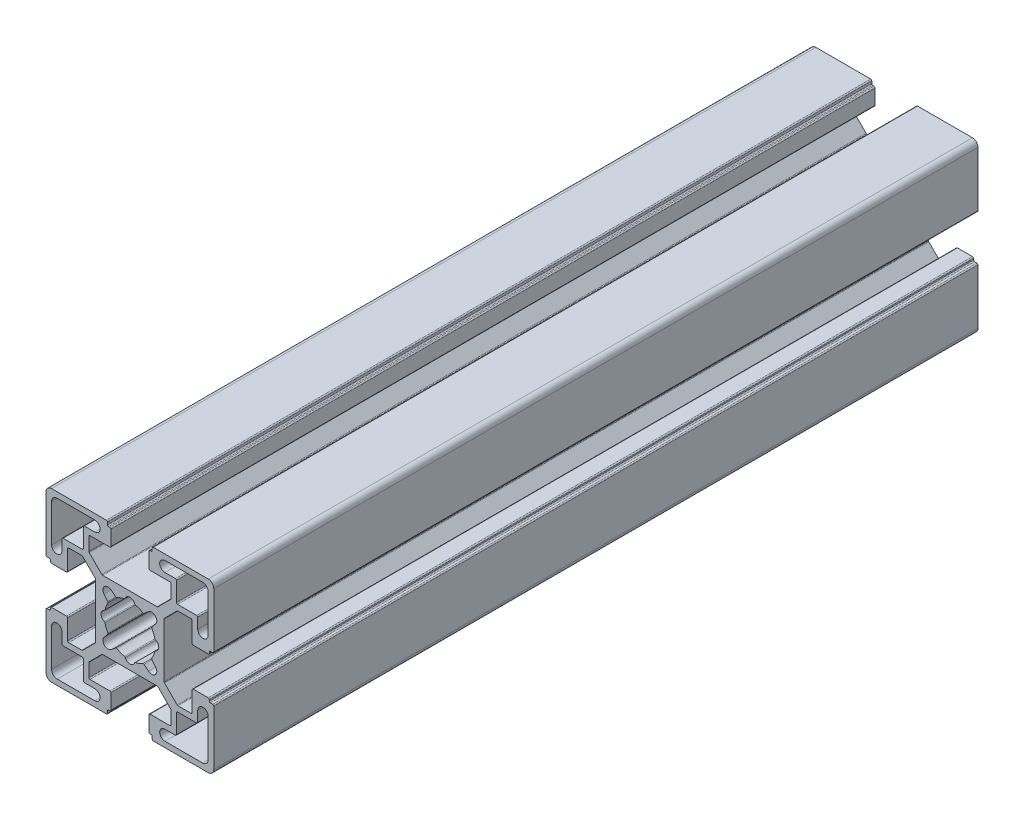
SolidWorks part; units mm, degrees
material "6063-T5"
ref_plane "Plane1" through (0, 0, 0) normal (0, 0, 1) x (1, 0, 0)
ref_plane "Plane2" through (0, 0, 0) normal (0, 1, 0) x (1, 0, 0)
ref_plane "Plane3" through (0, 0, 0) normal (1, 0, 0) x (0, 0, -1)
sketch "Sketch1" plane through (0, 0, 0) normal (0, 0, 1) x (1, 0, 0)
  line L0 (-3.8182, 5.9298) -> (-5.0112, 6.9114)
  line L1 (-6.9114, 5.0112) -> (-5.9298, 3.8182)
  line L2 (-5.9298, -3.8182) -> (-6.9114, -5.0112)
  line L3 (-5.0112, -6.9114) -> (-3.8182, -5.9298)
  line L4 (3.8182, -5.9298) -> (5.0112, -6.9114)
  line L5 (6.9114, -5.0112) -> (5.9298, -3.8182)
  line L6 (5.9298, 3.8182) -> (6.9114, 5.0112)
  line L7 (5.0112, 6.9114) -> (3.8182, 5.9298)
  line L8 (-19.5, -21) -> (-9.4, -21)
  line L9 (-9.4, -18.2) -> (-12.2, -18.2)
  line L10 (-12.5, -17.9) -> (-12.5, -12.8)
  line L11 (-12.8, -12.5) -> (-17.9, -12.5)
  line L12 (-18.2, -12.2) -> (-18.2, -9.4)
  line L13 (-21, -9.4) -> (-21, -19.5)
  line L14 (17.9, -12.5) -> (12.8, -12.5)
  line L15 (12.5, -12.8) -> (12.5, -17.9)
  line L16 (12.2, -18.2) -> (9.4, -18.2)
  line L17 (9.4, -21) -> (19.5, -21)
  line L18 (21, -19.5) -> (21, -9.4)
  line L19 (18.2, -9.4) -> (18.2, -12.2)
  line L20 (19.5, 21) -> (9.4, 21)
  line L21 (9.4, 18.2) -> (12.2, 18.2)
  line L22 (12.5, 17.9) -> (12.5, 12.8)
  line L23 (12.8, 12.5) -> (17.9, 12.5)
  line L24 (18.2, 12.2) -> (18.2, 9.4)
  line L25 (21, 9.4) -> (21, 19.5)
  line L26 (-18.2, 9.4) -> (-18.2, 12.2)
  line L27 (-17.9, 12.5) -> (-12.8, 12.5)
  line L28 (-12.5, 12.8) -> (-12.5, 17.9)
  line L29 (-12.2, 18.2) -> (-9.4, 18.2)
  line L30 (-9.4, 21) -> (-19.5, 21)
  line L31 (-21, 19.5) -> (-21, 9.4)
  line L32 (22.5, 6.3) -> (22.5, 21)
  line L33 (21.6, 6) -> (22.2, 6)
  line L34 (21.3, 5.4) -> (21.3, 5.7)
  line L36 (16.7, 10.7) -> (16.7, 5.4)
  line L37 (12.892, 11) -> (16.4, 11)
  line L38 (9.2879, 7.5201) -> (12.6799, 10.9121)
  line L39 (9.2, -7.308) -> (9.2, 7.308)
  line L40 (12.6799, -10.9121) -> (9.2879, -7.5201)
  line L41 (16.4, -11) -> (12.892, -11)
  line L42 (16.7, -5.4) -> (16.7, -10.7)
  line L44 (21.3, -5.7) -> (21.3, -5.4)
  line L45 (22.2, -6) -> (21.6, -6)
  line L46 (22.5, -21) -> (22.5, -6.3)
  line L47 (6.3, -22.5) -> (21, -22.5)
  line L48 (6, -21.6) -> (6, -22.2)
  line L49 (5.4, -21.3) -> (5.7, -21.3)
  line L51 (10.7, -16.7) -> (5.4, -16.7)
  line L52 (11, -12.892) -> (11, -16.4)
  line L53 (7.5201, -9.2879) -> (10.9121, -12.6799)
  line L54 (-7.4322, -9.2) -> (7.308, -9.2)
  line L55 (-10.9121, -12.6799) -> (-7.4322, -9.2)
  line L56 (-11, -16.4) -> (-11, -12.892)
  line L57 (-5.4, -16.7) -> (-10.7, -16.7)
  line L59 (-5.7, -21.3) -> (-5.4, -21.3)
  line L60 (-6, -22.2) -> (-6, -21.6)
  line L61 (-21, -22.5) -> (-6.3, -22.5)
  line L62 (-22.5, -6.3) -> (-22.5, -21)
  line L63 (-21.6, -6) -> (-22.2, -6)
  line L64 (-21.3, -5.4) -> (-21.3, -5.7)
  line L66 (-16.7, -10.7) -> (-16.7, -5.4)
  line L67 (-12.892, -11) -> (-16.4, -11)
  line L68 (-9.2879, -7.5201) -> (-12.6799, -10.9121)
  line L69 (-9.2, 7.308) -> (-9.2, -7.308)
  line L70 (-12.6799, 10.9121) -> (-9.2879, 7.5201)
  line L71 (-16.4, 11) -> (-12.892, 11)
  line L72 (-16.7, 5.4) -> (-16.7, 10.7)
  line L74 (-21.3, 5.7) -> (-21.3, 5.4)
  line L75 (-22.2, 6) -> (-21.6, 6)
  line L76 (-22.5, 21) -> (-22.5, 6.3)
  line L77 (-6.3, 22.5) -> (-21, 22.5)
  line L78 (-6, 21.6) -> (-6, 22.2)
  line L79 (-5.4, 21.3) -> (-5.7, 21.3)
  line L81 (-10.7, 16.7) -> (-5.4, 16.7)
  line L82 (-11, 12.892) -> (-11, 16.4)
  line L83 (-7.5201, 9.2879) -> (-10.9121, 12.6799)
  line L84 (7.308, 9.2) -> (-7.308, 9.2)
  line L85 (10.9121, 12.6799) -> (7.5201, 9.2879)
  line L86 (11, 16.4) -> (11, 12.892)
  line L87 (5.4, 16.7) -> (10.7, 16.7)
  line L89 (5.7, 21.3) -> (5.4, 21.3)
  line L90 (6, 22.2) -> (6, 21.6)
  line L91 (21, 22.5) -> (6.3, 22.5)
  line L92 (-5.1, 17) -> (-5.1, 21)
  line L93 (-21, 5.1) -> (-17, 5.1)
  line L94 (-17, -5.1) -> (-21, -5.1)
  line L95 (-5.1, -21) -> (-5.1, -17)
  line L96 (5.1, -17) -> (5.1, -21)
  line L97 (21, -5.1) -> (17, -5.1)
  line L98 (17, 5.1) -> (21, 5.1)
  line L99 (5.1, 21) -> (5.1, 17)
  arc A0 (-1.4794, 6.6883) -> (-1.2635, 6.8756) centre (-1.5442, 6.9813) ccw
  arc A1 (-1.4794, 6.6883) -> (-3.4754, 5.9029) centre (0, 0) ccw
  arc A2 (-3.8182, 5.9298) -> (-3.4754, 5.9029) centre (-3.6276, 6.1614) ccw
  arc A3 (-5.0112, 6.9114) -> (-6.9114, 5.0112) centre (-5.869, 5.869) ccw
  arc A4 (-5.9029, 3.4754) -> (-5.9298, 3.8182) centre (-6.1614, 3.6276) ccw
  arc A5 (-5.9029, 3.4754) -> (-6.6883, 1.4794) centre (0, 0) ccw
  arc A6 (-6.8756, 1.2635) -> (-6.6883, 1.4794) centre (-6.9813, 1.5442) ccw
  arc A7 (-6.8756, 1.2635) -> (-6.8756, -1.2635) centre (-6.4, 0) ccw
  arc A8 (-6.6883, -1.4794) -> (-6.8756, -1.2635) centre (-6.9813, -1.5442) ccw
  arc A9 (-6.6883, -1.4794) -> (-5.9029, -3.4754) centre (0, 0) ccw
  arc A10 (-5.9298, -3.8182) -> (-5.9029, -3.4754) centre (-6.1614, -3.6276) ccw
  arc A11 (-6.9114, -5.0112) -> (-5.0112, -6.9114) centre (-5.869, -5.869) ccw
  arc A12 (-3.4754, -5.9029) -> (-3.8182, -5.9298) centre (-3.6276, -6.1614) ccw
  arc A13 (-3.4754, -5.9029) -> (-1.4794, -6.6883) centre (0, 0) ccw
  arc A14 (-1.2635, -6.8756) -> (-1.4794, -6.6883) centre (-1.5442, -6.9812) ccw
  arc A15 (-1.2635, -6.8756) -> (1.2635, -6.8756) centre (0, -6.4) ccw
  arc A16 (1.4794, -6.6883) -> (1.2635, -6.8756) centre (1.5442, -6.9812) ccw
  arc A17 (1.4794, -6.6883) -> (3.4754, -5.9029) centre (0, 0) ccw
  arc A18 (3.8182, -5.9298) -> (3.4754, -5.9029) centre (3.6276, -6.1614) ccw
  arc A19 (5.0112, -6.9114) -> (6.9114, -5.0112) centre (5.869, -5.869) ccw
  arc A20 (5.9029, -3.4754) -> (5.9298, -3.8182) centre (6.1614, -3.6276) ccw
  arc A21 (5.9029, -3.4754) -> (6.6883, -1.4794) centre (0, 0) ccw
  arc A22 (6.8756, -1.2635) -> (6.6883, -1.4794) centre (6.9812, -1.5442) ccw
  arc A23 (6.8756, -1.2635) -> (6.8756, 1.2635) centre (6.4, 0) ccw
  arc A24 (6.6883, 1.4794) -> (6.8756, 1.2635) centre (6.9812, 1.5442) ccw
  arc A25 (6.6883, 1.4794) -> (5.9029, 3.4754) centre (0, 0) ccw
  arc A26 (5.9298, 3.8182) -> (5.9029, 3.4754) centre (6.1614, 3.6276) ccw
  arc A27 (6.9114, 5.0112) -> (5.0112, 6.9114) centre (5.869, 5.869) ccw
  arc A28 (3.4754, 5.9029) -> (3.8182, 5.9298) centre (3.6276, 6.1614) ccw
  arc A29 (3.4754, 5.9029) -> (1.4794, 6.6883) centre (0, 0) ccw
  arc A30 (1.2635, 6.8756) -> (1.4794, 6.6883) centre (1.5442, 6.9813) ccw
  arc A31 (1.2635, 6.8756) -> (-1.2635, 6.8756) centre (0, 6.4) ccw
  arc A32 (-21, -19.5) -> (-19.5, -21) centre (-19.5, -19.5) ccw
  arc A33 (-9.4, -21) -> (-9.4, -18.2) centre (-9.4, -19.6) ccw
  arc A34 (-12.5, -17.9) -> (-12.2, -18.2) centre (-12.2, -17.9) ccw
  arc A35 (-12.5, -12.8) -> (-12.8, -12.5) centre (-12.8, -12.8) ccw
  arc A36 (-18.2, -12.2) -> (-17.9, -12.5) centre (-17.9, -12.2) ccw
  arc A37 (-18.2, -9.4) -> (-21, -9.4) centre (-19.6, -9.4) ccw
  arc A38 (17.9, -12.5) -> (18.2, -12.2) centre (17.9, -12.2) ccw
  arc A39 (12.8, -12.5) -> (12.5, -12.8) centre (12.8, -12.8) ccw
  arc A40 (12.2, -18.2) -> (12.5, -17.9) centre (12.2, -17.9) ccw
  arc A41 (9.4, -18.2) -> (9.4, -21) centre (9.4, -19.6) ccw
  arc A42 (19.5, -21) -> (21, -19.5) centre (19.5, -19.5) ccw
  arc A43 (21, -9.4) -> (18.2, -9.4) centre (19.6, -9.4) ccw
  arc A44 (21, 19.5) -> (19.5, 21) centre (19.5, 19.5) ccw
  arc A45 (9.4, 21) -> (9.4, 18.2) centre (9.4, 19.6) ccw
  arc A46 (12.5, 17.9) -> (12.2, 18.2) centre (12.2, 17.9) ccw
  arc A47 (12.5, 12.8) -> (12.8, 12.5) centre (12.8, 12.8) ccw
  arc A48 (18.2, 12.2) -> (17.9, 12.5) centre (17.9, 12.2) ccw
  arc A49 (18.2, 9.4) -> (21, 9.4) centre (19.6, 9.4) ccw
  arc A50 (-21, 9.4) -> (-18.2, 9.4) centre (-19.6, 9.4) ccw
  arc A51 (-17.9, 12.5) -> (-18.2, 12.2) centre (-17.9, 12.2) ccw
  arc A52 (-12.8, 12.5) -> (-12.5, 12.8) centre (-12.8, 12.8) ccw
  arc A53 (-12.2, 18.2) -> (-12.5, 17.9) centre (-12.2, 17.9) ccw
  arc A54 (-9.4, 18.2) -> (-9.4, 21) centre (-9.4, 19.6) ccw
  arc A55 (-19.5, 21) -> (-21, 19.5) centre (-19.5, 19.5) ccw
  arc A56 (22.2, 6) -> (22.5, 6.3) centre (22.2, 6.3) ccw
  arc A57 (21.6, 6) -> (21.3, 5.7) centre (21.6, 5.7) ccw
  arc A58 (-17, -5.1) -> (-16.7, -5.4) centre (-17, -5.4) cw
  arc A59 (16.7, 10.7) -> (16.4, 11) centre (16.4, 10.7) ccw
  arc A60 (12.892, 11) -> (12.6799, 10.9121) centre (12.892, 10.7) ccw
  arc A61 (9.2879, 7.5201) -> (9.2, 7.308) centre (9.5, 7.308) ccw
  arc A62 (9.2, -7.308) -> (9.2879, -7.5201) centre (9.5, -7.308) ccw
  arc A63 (12.6799, -10.9121) -> (12.892, -11) centre (12.892, -10.7) ccw
  arc A64 (16.4, -11) -> (16.7, -10.7) centre (16.4, -10.7) ccw
  arc A65 (-17, 5.1) -> (-16.7, 5.4) centre (-17, 5.4) ccw
  arc A66 (21.3, -5.7) -> (21.6, -6) centre (21.6, -5.7) ccw
  arc A67 (22.5, -6.3) -> (22.2, -6) centre (22.2, -6.3) ccw
  arc A68 (21, -22.5) -> (22.5, -21) centre (21, -21) ccw
  arc A69 (6, -22.2) -> (6.3, -22.5) centre (6.3, -22.2) ccw
  arc A70 (6, -21.6) -> (5.7, -21.3) centre (5.7, -21.6) ccw
  arc A71 (-5.1, 17) -> (-5.4, 16.7) centre (-5.4, 17) cw
  arc A72 (10.7, -16.7) -> (11, -16.4) centre (10.7, -16.4) ccw
  arc A73 (11, -12.892) -> (10.9121, -12.6799) centre (10.7, -12.892) ccw
  arc A74 (7.5201, -9.2879) -> (7.308, -9.2) centre (7.308, -9.5) ccw
  arc A75 (-10.9121, -12.6799) -> (-11, -12.892) centre (-10.7, -12.892) ccw
  arc A76 (-11, -16.4) -> (-10.7, -16.7) centre (-10.7, -16.4) ccw
  arc A77 (5.1, 17) -> (5.4, 16.7) centre (5.4, 17) ccw
  arc A78 (-5.7, -21.3) -> (-6, -21.6) centre (-5.7, -21.6) ccw
  arc A79 (-6.3, -22.5) -> (-6, -22.2) centre (-6.3, -22.2) ccw
  arc A80 (-22.5, -21) -> (-21, -22.5) centre (-21, -21) ccw
  arc A81 (-22.2, -6) -> (-22.5, -6.3) centre (-22.2, -6.3) ccw
  arc A82 (-21.6, -6) -> (-21.3, -5.7) centre (-21.6, -5.7) ccw
  arc A83 (16.7, 5.4) -> (17, 5.1) centre (17, 5.4) ccw
  arc A84 (-16.7, -10.7) -> (-16.4, -11) centre (-16.4, -10.7) ccw
  arc A85 (-12.892, -11) -> (-12.6799, -10.9121) centre (-12.892, -10.7) ccw
  arc A86 (-9.2879, -7.5201) -> (-9.2, -7.308) centre (-9.5, -7.308) ccw
  arc A87 (-9.2, 7.308) -> (-9.2879, 7.5201) centre (-9.5, 7.308) ccw
  arc A88 (-12.6799, 10.9121) -> (-12.892, 11) centre (-12.892, 10.7) ccw
  arc A89 (-16.4, 11) -> (-16.7, 10.7) centre (-16.4, 10.7) ccw
  arc A90 (17, -5.1) -> (16.7, -5.4) centre (17, -5.4) ccw
  arc A91 (-21.3, 5.7) -> (-21.6, 6) centre (-21.6, 5.7) ccw
  arc A92 (-22.5, 6.3) -> (-22.2, 6) centre (-22.2, 6.3) ccw
  arc A93 (-21, 22.5) -> (-22.5, 21) centre (-21, 21) ccw
  arc A94 (-6, 22.2) -> (-6.3, 22.5) centre (-6.3, 22.2) ccw
  arc A95 (-6, 21.6) -> (-5.7, 21.3) centre (-5.7, 21.6) ccw
  arc A96 (5.1, -17) -> (5.4, -16.7) centre (5.4, -17) cw
  arc A97 (-10.7, 16.7) -> (-11, 16.4) centre (-10.7, 16.4) ccw
  arc A98 (-11, 12.892) -> (-10.9121, 12.6799) centre (-10.7, 12.892) ccw
  arc A99 (-7.5201, 9.2879) -> (-7.308, 9.2) centre (-7.308, 9.5) ccw
  arc A100 (7.308, 9.2) -> (7.5201, 9.2879) centre (7.308, 9.5) ccw
  arc A101 (10.9121, 12.6799) -> (11, 12.892) centre (10.7, 12.892) ccw
  arc A102 (11, 16.4) -> (10.7, 16.7) centre (10.7, 16.4) ccw
  arc A103 (-5.1, -17) -> (-5.4, -16.7) centre (-5.4, -17) ccw
  arc A104 (5.7, 21.3) -> (6, 21.6) centre (5.7, 21.6) ccw
  arc A105 (6.3, 22.5) -> (6, 22.2) centre (6.3, 22.2) ccw
  arc A106 (22.5, 21) -> (21, 22.5) centre (21, 21) ccw
  arc A107 (-21, 5.1) -> (-21.3, 5.4) centre (-21, 5.4) cw
  arc A108 (-21, -5.1) -> (-21.3, -5.4) centre (-21, -5.4) ccw
  arc A109 (-5.1, -21) -> (-5.4, -21.3) centre (-5.4, -21) cw
  arc A110 (5.1, -21) -> (5.4, -21.3) centre (5.4, -21) ccw
  arc A111 (21, -5.1) -> (21.3, -5.4) centre (21, -5.4) cw
  arc A112 (21, 5.1) -> (21.3, 5.4) centre (21, 5.4) ccw
  arc A113 (5.1, 21) -> (5.4, 21.3) centre (5.4, 21) cw
  arc A114 (-5.1, 21) -> (-5.4, 21.3) centre (-5.4, 21) ccw
  point P299 (0, 22.5)
  point P300 (22.5, 22.5)
  point P301 (-22.5, 22.5)
  point P302 (-22.5, 0)
  point P303 (-22.5, -22.5)
  point P304 (0, -22.5)
  point P305 (22.5, -22.5)
  point P306 (22.5, 0)
  point P308 (0, 0)
  dimension "D1" = 0.3
extrude "Ressalto-extrusão2" add sketch "Sketch1" along normal blind 205 contours L32 A106 L91 A105 L90 A104 L89 L99 A77 L87 A102 L86 A101 L85 A100 L84 A99 L83 A98 L82 A97 L81 A71 L92 L79 A95 L78 A94 L77 A93 L76 A92 L75 A91 L74 L93 A65 L72 A89 L71 A88 L70 A87 L69 A86 L68 A85 L67 A84 L66 A58 region at (21.9621, 6.5379, 0)
